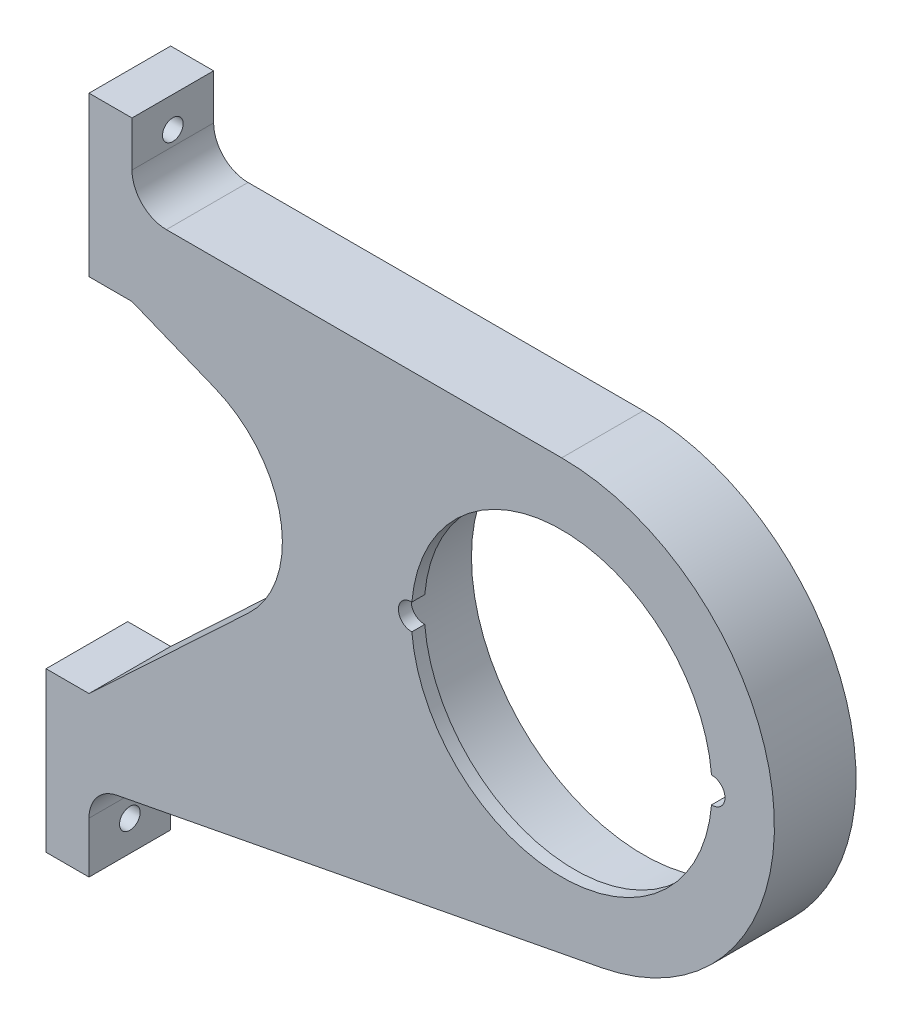
SolidWorks part; units mm, degrees
material "6061 Alloy"
ref_plane "Front Plane" through (0, 0, 0) normal (0, 0, 1) x (1, 0, 0)
ref_plane "Top Plane" through (0, 0, 0) normal (0, 1, 0) x (1, 0, 0)
ref_plane "Right Plane" through (0, 0, 0) normal (1, 0, 0) x (0, 0, -1)
sketch "Sketch1" plane through (0, 0, 0) normal (0, 0, 1) x (1, 0, 0)
  line L0 (-139.7, 86.36) -> (-139.7, 39.37)
  line L1 (-139.7, 39.37) -> (-127, 39.37)
  line L2 (-139.7, 86.36) -> (-127, 86.36)
  line L3 (-127, 86.36) -> (-127, 62.865)
  line L4 (-127, 62.865) -> (0, 62.865)
  line L5 (-152.4, -67.31) -> (-139.7, -67.31)
  line L6 (-152.4, -67.31) -> (-152.4, -114.3)
  line L7 (-152.4, -114.3) -> (-139.7, -114.3)
  line L8 (-139.7, -114.3) -> (-139.7, -90.805)
  line L9 (-139.7, -90.805) -> (11.8415, -61.7397)
  line L10 (-127, 39.37) -> (-102.411, 29.44)
  line L11 (-139.7, -67.31) -> (-92.591, -23.1685)
  circle A1 centre (0, 0) radius 50.8
  arc A2 (-92.591, -23.1685) -> (-102.411, 29.44) centre (-114.3, 0) ccw
  arc A7 (11.8415, -61.7397) -> (0, 62.865) centre (0, 0) ccw
  dimension "D2" = 101.6
  dimension "D13" = 63.5
  dimension "D14" = 31.75
  dimension "D15" = 12.065
  dimension "D3" = 46.99
  dimension "D4" = 12.7
  dimension "D5" = 23.495
  dimension "D6" = 139.7
  dimension "D7" = 12.7
  dimension "D8" = 12.7
  dimension "D9" = 46.99
  dimension "D10" = 23.495
  dimension "D12" = 114.3
extrude "Boss-Extrude1" add sketch "Sketch1" along normal blind 24.13
fillet "Fillet1" radius 10.16 2 edges at (-139.7, -90.805, 12.065) (-127, 62.865, 12.065)
sketch "Sketch2" plane through (-152.4, 0, 0) normal (-1, 0, 0) x (0, 0, 1)
  line L0 (24.13, 86.36) -> (0, 86.36) construction
  line L3 (24.13, -114.3) -> (0, -114.3) construction
  circle A0 centre (12.065, -105.283) radius 3.048
  circle A1 centre (12.065, 77.343) radius 3.048
  point P6 (12.065, 86.36)
  dimension "D1" = 6.096
  dimension "D3" = 5.969
  dimension "D2" = 5.969
extrude "Cut-Extrude1" cut sketch "Sketch2" against normal through all
sketch "Sketch3" plane through (0, 0, 24.13) normal (0, 0, 1) x (1, 0, 0)
  arc A0 (-44.2867, -3.8065) -> (44.2867, -3.8065) centre (0, 0) ccw
  arc A1 (-44.2867, 3.8065) -> (-44.2867, -3.8065) centre (-44.45, 0) ccw
  circle A2 centre (0, 0) radius 50.8 construction
  circle A3 centre (0, 0) radius 50.8
  arc A4 (44.2867, -3.8065) -> (44.2867, 3.8065) centre (44.45, 0) ccw
  arc A5 (44.2867, 3.8065) -> (-44.2867, 3.8065) centre (0, 0) ccw
  circle M24 centre (0, 0) radius 50.8
  dimension "D1" = 88.9
  dimension "D2" = 2.54
  dimension "D3" = 2.54
extrude "Boss-Extrude2" add sketch "Sketch3" against normal blind 3.81 contours A5 A4 A1 M24 | A4 A0 A1 A3 region at (-49.3632, 0, 24.13)
